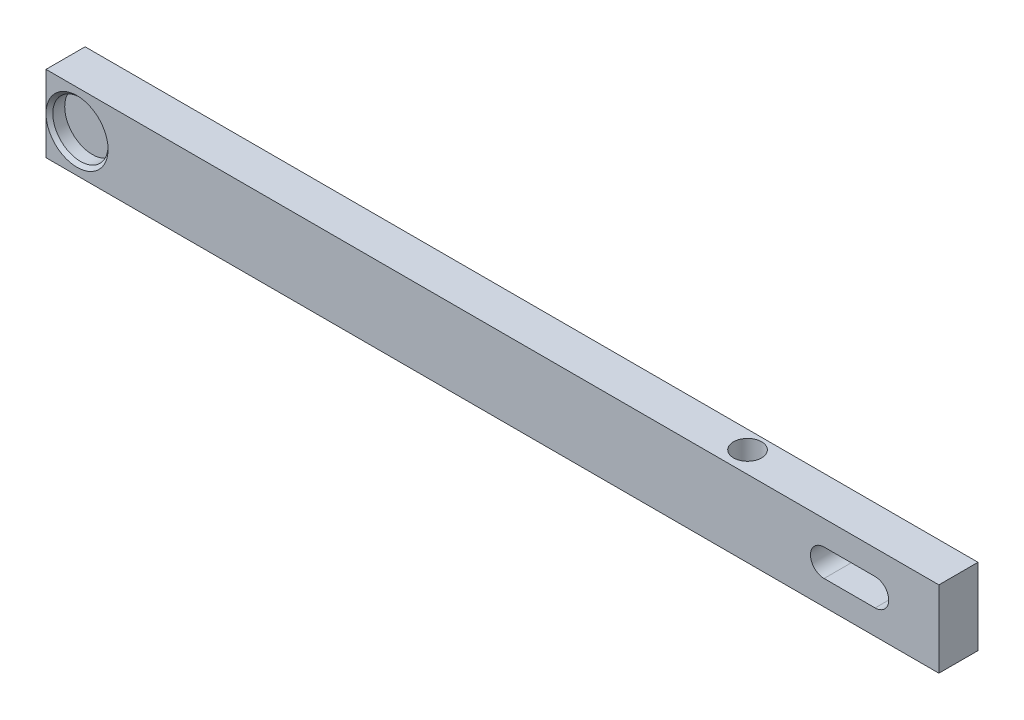
SolidWorks part; units mm, degrees
ref_plane "Front" through (0, 0, 0) normal (0, 0, 1) x (1, 0, 0)
ref_plane "Top" through (0, 0, 0) normal (0, 1, 0) x (1, 0, 0)
ref_plane "Right" through (0, 0, 0) normal (1, 0, 0) x (0, 0, -1)
sketch "Sketch1" plane through (0, 0, 0) normal (0, 0, 1) x (1, 0, 0)
  line L1 (52.5, -4.5) -> (-52.5, -4.5)
  line L2 (52.5, -4.5) -> (52.5, 4.5)
  line L3 (52.5, 4.5) -> (-52.5, 4.5)
  line L4 (-52.5, -4.5) -> (-52.5, 4.5)
  line L5 (52.5, -4.5) -> (-52.5, 4.5) construction
  line L6 (52.5, 4.5) -> (-52.5, -4.5) construction
  point P0 (0, 0)
  dimension "D1" = 9
  dimension "D2" = 105
extrude "Boss-Extrude1" add sketch "Sketch1" along normal blind 5
sketch "Sketch2" plane through (0, 4.5, 0) normal (0, 1, 0) x (1, 0, 0)
  line L0 (52.5, -5) -> (52.5, 0) construction
  line L2 (52.5, 0) -> (-52.5, 0) construction
  circle A0 centre (27.5, -2.5) radius 1.65
  dimension "D3" = 3.3
  dimension "D2" = 25
  dimension "D1" = 2.5
sketch "Sketch4" plane through (0, 0, 5) normal (0, 0, 1) x (1, 0, 0)
  line L0 (39, 0) -> (45, 0) construction
  line L1 (39, 1.6) -> (45, 1.6)
  line L2 (39, -1.6) -> (45, -1.6)
  arc A0 (39, 1.6) -> (39, -1.6) centre (39, 0) ccw
  arc A1 (45, -1.6) -> (45, 1.6) centre (45, 0) ccw
  point P2 (42, 0)
  dimension "D1" = 1.6
  dimension "D2" = 42
  dimension "D3" = 6
extrude "Cut-Extrude1" cut sketch "Sketch4" against normal blind 5
ref_plane "Plane1" through (-48.5, 0, 0) normal (-1, 0, 0) x (0, 0, 1)
sketch "Sketch7" plane through (0, 0, 5) normal (0, 0, -1) x (-1, 0, 0)
  line L1 (52.5, 4.5) -> (52.5, -4.5) construction
  circle A0 centre (48.85, 0) radius 3.25
  dimension "D1" = 6.5
  dimension "D2" = 3.65
extrude "Cut-Extrude2" cut sketch "Sketch7" along normal blind 1.8
chamfer "Chamfer1" distance 0.4 angle 45 1 edges at (-52.1, 0, 5)
chamfer "Chamfer2" distance 0.4 angle 45 8 edges at (52.5, 0, 0) (0, 4.5, 0) (-52.5, 0, 0) (0, -4.5, 0) (46.6, 0, 0) (42, -1.6, 0) (37.4, 0, 0) (42, 1.6, 0)
extrude "Cut-Extrude3" cut sketch "Sketch2" against normal blind 10
